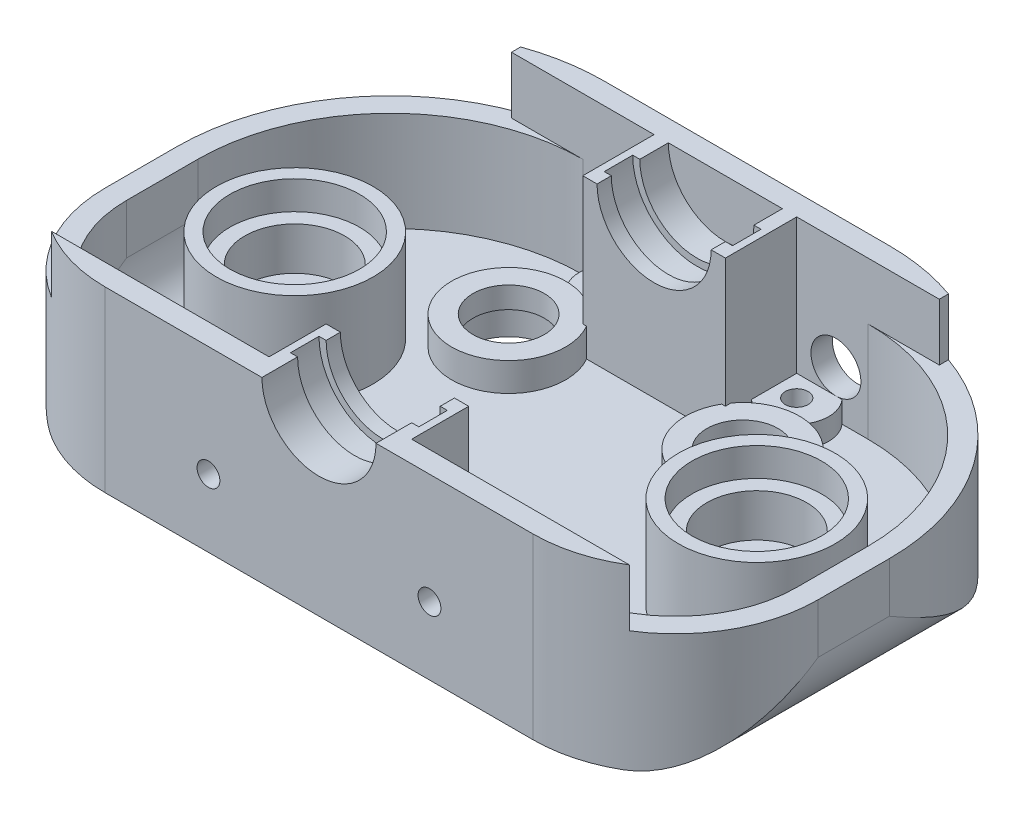
SolidWorks part; units mm, degrees
ref_plane "Front Plane" through (0, 0, 0) normal (0, 0, 1) x (1, 0, 0)
ref_plane "Top Plane" through (0, 0, 0) normal (0, 1, 0) x (1, 0, 0)
ref_plane "Right Plane" through (0, 0, 0) normal (1, 0, 0) x (0, 0, -1)
other "Configuration Table"
sketch "草图1" plane through (0, 0, 0) normal (0, 1, 0) x (1, 0, 0)
  line L5 (-50, 30) -> (50, 30)
  line L6 (-50, 30) -> (-50, -30)
  line L7 (-50, -30) -> (50, -30)
  line L8 (50, 30) -> (50, -30)
  line L9 (-50, 30) -> (50, -30) construction
  line L10 (-50, -30) -> (50, 30) construction
  point P0 (0, 0)
  dimension "D1" = 100
  dimension "D2" = 60
extrude "凸台-拉伸1" add sketch "草图1" along normal blind 25
fillet "圆角2" radius 10 2 edges at (50, 0, 0) (-50, 0, 0)
fillet "圆角1" radius 20 2 edges at (50, 17.5, 30) (-50, 17.5, 30)
fillet "圆角3" radius 30 2 edges at (50, 17.5, -30) (-50, 17.5, -30)
shell "抽壳1" thickness 3
sketch "草图2" plane through (0, 0, 27) normal (0, 0, -1) x (-1, 0, 0)
  line L0 (-20, 25) -> (20, 25) construction
  circle A0 centre (-15.5, 9.5) radius 1.6
  circle A1 centre (15.5, 9.5) radius 1.6
  dimension "D4" = 3.2
  dimension "D5" = 3.2
  dimension "D1" = 15.5
  dimension "D2" = 31
  dimension "D3" = 15.5
extrude "切除-拉伸1" cut sketch "草图2" against normal through all both and the other way through all
sketch "草图3" plane through (-50, 0, 0) normal (-1, 0, 0) x (0, 0, 1)
  line L0 (0, 25) -> (10, 25) construction
  line L1 (-27, 27.6853) -> (27, 27.6853)
  line L2 (-27, 27.6853) -> (-27, 17)
  line L3 (-27, 17) -> (27, 17)
  line L4 (27, 27.6853) -> (27, 17)
  line L6 (-30, 25) -> (-30, 10) construction
  line L7 (30, 25) -> (30, 0) construction
  dimension "D1" = 8
  dimension "D2" = 3
  dimension "D3" = 3
extrude "切除-拉伸2" cut sketch "草图3" against normal through all
sketch "草图5" plane through (0, 0, 27) normal (0, 0, -1) x (-1, 0, 0)
  line L0 (-20, 25) -> (20, 25) construction
  line L1 (-10, 25) -> (10, 25)
  line L2 (-10, 25) -> (-10, 3)
  line L3 (-10, 3) -> (10, 3)
  line L4 (10, 25) -> (10, 3)
  line L5 (-20, 0) -> (20, 0) construction
  dimension "D1" = 3
  dimension "D2" = 20
  dimension "D3" = 10
extrude "凸台-拉伸3" add sketch "草图5" along normal up to surface (54 mm away)
sketch "草图6" plane through (0, 25, 0) normal (0, 1, 0) x (1, 0, 0)
  line L0 (-10, 27) -> (-10, -27) construction
  line L1 (-10, 17) -> (10, 17)
  line L2 (-10, 17) -> (-10, -19)
  line L3 (-10, -19) -> (10, -19)
  line L4 (10, 17) -> (10, -19)
  line L5 (10, 27) -> (10, -27) construction
  line L6 (-30, -27) -> (-10, -27) construction
  line L7 (10, -27) -> (40.5357, -27) construction
  dimension "D1" = 8
  dimension "D2" = 44
extrude "切除-拉伸4" cut sketch "草图6" against normal up to surface (22 mm away) up to face at (-25.1992, 3, 0.7143)
sketch "草图7" plane through (0, 0, 30) normal (0, 0, 1) x (1, 0, 0)
  line L0 (-30, 25) -> (30, 25) construction
  circle A0 centre (0, 25) radius 8
  dimension "D1" = 16
extrude "切除-拉伸5" cut sketch "草图7" against normal up to surface (57 mm away)
ref_plane "基准面1" through (0, 0, 25) normal (0, 0, -1) x (-1, 0, 0)
sketch "草图8" plane through (0, 0, 25) normal (0, 0, -1) x (-1, 0, 0)
  line L0 (-20, 25) -> (20, 25) construction
  circle A0 centre (0, 25) radius 9
  dimension "D1" = 18
extrude "切除-拉伸6" cut sketch "草图8" along normal blind 4
ref_plane "基准面2" through (0, 0, -19) normal (0, 0, 1) x (1, 0, 0)
sketch "草图9" plane through (0, 0, -19) normal (0, 0, 1) x (1, 0, 0)
  line L0 (-8, 25) -> (8, 25) construction
  circle A0 centre (0, 25) radius 9
  dimension "D1" = 18
extrude "切除-拉伸7" cut sketch "草图9" against normal blind 4
sketch "草图11" plane through (0, 3, 0) normal (0, 1, 0) x (1, 0, 0)
  line L0 (8, -30) -> (30, -30) construction
  circle A0 centre (-32.4, -1) radius 11
  circle A1 centre (32.4, -1) radius 11
  dimension "D4" = 22
  dimension "D5" = 22
  dimension "D1" = 64.8
  dimension "D2" = 32.4
  dimension "D3" = 29
extrude "凸台-拉伸4" add sketch "草图11" along normal blind 13
sketch "草图12" plane through (0, 16, 0) normal (0, 1, 0) x (1, 0, 0)
  circle A0 centre (-32.4, -1) radius 9.1
  circle A1 centre (32.4, -1) radius 9.1
  dimension "D1" = 18.2
  dimension "D2" = 18.2
extrude "切除-拉伸8" cut sketch "草图12" against normal blind 4
sketch "草图13" plane through (0, 12, 0) normal (0, 1, 0) x (1, 0, 0)
  circle A0 centre (-32.4, -1) radius 7
  circle A1 centre (32.4, -1) radius 7
  dimension "D1" = 14
  dimension "D2" = 14
extrude "切除-拉伸9" cut sketch "草图13" against normal blind 6
sketch "草图14" plane through (0, 3, 0) normal (0, 1, 0) x (1, 0, 0)
  line L0 (10, -27) -> (40.5357, -27) construction
  circle A1 centre (13, -22) radius 4.5
  circle A2 centre (-13, -22) radius 4.5
  circle A3 centre (-13, 24) radius 4.5
  circle A4 centre (13, 24) radius 4.5
  dimension "D1" = 13
  dimension "D2" = 9
  dimension "D3" = 5
  dimension "D4" = 2
  dimension "D5" = 2
extrude "凸台-拉伸6" add sketch "草图14" along normal blind 3
sketch "草图16" plane through (0, 6, 0) normal (0, 1, 0) x (1, 0, 0)
  circle A0 centre (13, -22) radius 1.6
  circle A1 centre (-13, -22) radius 1.6
  circle A2 centre (-13, 24) radius 1.6
  circle A3 centre (13, 24) radius 1.6
  dimension "D1" = 3.2
  dimension "D2" = 3.2
  dimension "D3" = 3.2
  dimension "D4" = 3.2
extrude "切除-拉伸13" cut sketch "草图16" against normal through all
sketch "草图18" plane through (0, 0, -30) normal (0, 0, -1) x (-1, 0, 0)
  line L1 (-50, 25) -> (-30, 25)
  line L2 (-50, 25) -> (-50, 17)
  line L3 (-50, 17) -> (-30, 17)
  line L4 (-30, 25) -> (-30, 17)
  line L5 (50, 25) -> (30, 25)
  line L6 (50, 25) -> (50, 17)
  line L7 (50, 17) -> (30, 17)
  line L8 (30, 25) -> (30, 17)
  dimension "D1" = 8
  dimension "D2" = 20
  dimension "D3" = 8
  dimension "D4" = 20
extrude "切除-拉伸15" cut sketch "草图18" against normal blind 10
sketch "草图20" plane through (0, 6, 0) normal (0, 1, 0) x (1, 0, 0)
  circle A0 centre (-32.4, -1) radius 1.6
  circle A1 centre (32.4, -1) radius 1.6
  dimension "D1" = 3.2
  dimension "D2" = 3.2
extrude "切除-拉伸16" cut sketch "草图20" against normal blind 10
sketch "草图21" plane through (0, 0, 0) normal (0, -1, 0) x (1, 0, 0)
  circle A0 centre (16.4, -13) radius 8
  circle A1 centre (-16.4, -13) radius 8
  point P0 (32.4, 1)
  point P1 (16.4, -13)
  point P7 (0, 0)
  point P9 (18.4, -7.3173)
  dimension "D3" = 16
  dimension "D4" = 16
  dimension "D1" = 16
  dimension "D2" = 14
  dimension "D5" = 32.8
extrude "凸台-拉伸7" add sketch "草图21" against normal blind 7
sketch "草图25" plane through (0, 7, 0) normal (0, 1, 0) x (1, 0, 0)
  circle A0 centre (-16.4, 13) radius 5
  circle A1 centre (16.4, 13) radius 5
  dimension "D1" = 10
  dimension "D2" = 10
extrude "切除-拉伸19" cut sketch "草图25" against normal through all both and the other way through all
sketch "草图26" plane through (0, 0, 0) normal (0, -1, 0) x (1, 0, 0)
  circle A0 centre (-16.4, -13) radius 6
  circle A1 centre (16.4, -13) radius 6
  dimension "D1" = 12
  dimension "D2" = 12
extrude "切除-拉伸20" cut sketch "草图26" against normal blind 4
sketch "草图27" plane through (0, 0, -30) normal (0, 0, -1) x (-1, 0, 0)
  circle A0 centre (-15.5, 9.5) radius 3.5
  circle A1 centre (15.5, 9.5) radius 3.5
  dimension "D1" = 7
  dimension "D2" = 7
extrude "切除-拉伸21" cut sketch "草图27" against normal mid plane 10
sketch "草图17" plane through (0, 0, 0) normal (0, -1, 0) x (1, 0, 0)
  line L1 (-11.3371, 19.0934) -> (-9.6514, 21.9868)
  line L2 (-9.6514, 21.9868) -> (-11.3143, 24.8934)
  line L3 (-11.3143, 24.8934) -> (-14.6629, 24.9066)
  line L4 (-14.6629, 24.9066) -> (-16.3486, 22.0132)
  line L5 (-16.3486, 22.0132) -> (-14.6857, 19.1066)
  line L6 (-14.6857, 19.1066) -> (-11.3371, 19.0934)
  line L7 (14.7176, 19.1254) -> (16.3483, 22.0502)
  line L8 (16.3483, 22.0502) -> (14.6306, 24.9248)
  line L9 (14.6306, 24.9248) -> (11.2824, 24.8746)
  line L10 (11.2824, 24.8746) -> (9.6517, 21.9498)
  line L11 (9.6517, 21.9498) -> (11.3694, 19.0752)
  line L12 (11.3694, 19.0752) -> (14.7176, 19.1254)
  line L13 (-11.5244, -27.006) -> (-9.6589, -24.2251)
  line L14 (-9.6589, -24.2251) -> (-11.1345, -21.2191)
  line L15 (-11.1345, -21.2191) -> (-14.4756, -20.994)
  line L16 (-14.4756, -20.994) -> (-16.3411, -23.7749)
  line L17 (-16.3411, -23.7749) -> (-14.8655, -26.7809)
  line L18 (-14.8655, -26.7809) -> (-11.5244, -27.006)
  line L19 (15.8789, -25.7103) -> (15.9206, -22.362)
  line L20 (15.9206, -22.362) -> (13.0417, -20.6516)
  line L21 (13.0417, -20.6516) -> (10.1211, -22.2897)
  line L22 (10.1211, -22.2897) -> (10.0794, -25.638)
  line L23 (10.0794, -25.638) -> (12.9583, -27.3484)
  line L24 (12.9583, -27.3484) -> (15.8789, -25.7103)
  line L25 (35.1553, -0.9031) -> (35.4257, 2.4346)
  line L26 (35.4257, 2.4346) -> (32.6704, 4.3377)
  line L27 (32.6704, 4.3377) -> (29.6447, 2.9031)
  line L28 (29.6447, 2.9031) -> (29.3743, -0.4346)
  line L29 (29.3743, -0.4346) -> (32.1296, -2.3377)
  line L30 (32.1296, -2.3377) -> (35.1553, -0.9031)
  line L31 (-29.3423, -0.3651) -> (-29.6889, 2.9655)
  line L32 (-29.6889, 2.9655) -> (-32.7466, 4.3306)
  line L33 (-32.7466, 4.3306) -> (-35.4577, 2.3651)
  line L34 (-35.4577, 2.3651) -> (-35.1111, -0.9655)
  line L35 (-35.1111, -0.9655) -> (-32.0534, -2.3306)
  line L36 (-32.0534, -2.3306) -> (-29.3423, -0.3651)
  circle A4 centre (-13, 22) radius 2.9 construction
  circle A5 centre (13, 22) radius 2.9 construction
  circle A6 centre (-13, -24) radius 2.9 construction
  circle A7 centre (13, -24) radius 2.9 construction
  circle A8 centre (32.4, 1) radius 2.9 construction
  circle A9 centre (-32.4, 1) radius 2.9 construction
  dimension "D1" = 5.8
  dimension "D2" = 5.8
  dimension "D3" = 5.8
  dimension "D4" = 5.8
  dimension "D5" = 5.8
  dimension "D6" = 5.8
extrude "切除-拉伸14" cut sketch "草图17" against normal blind 3
